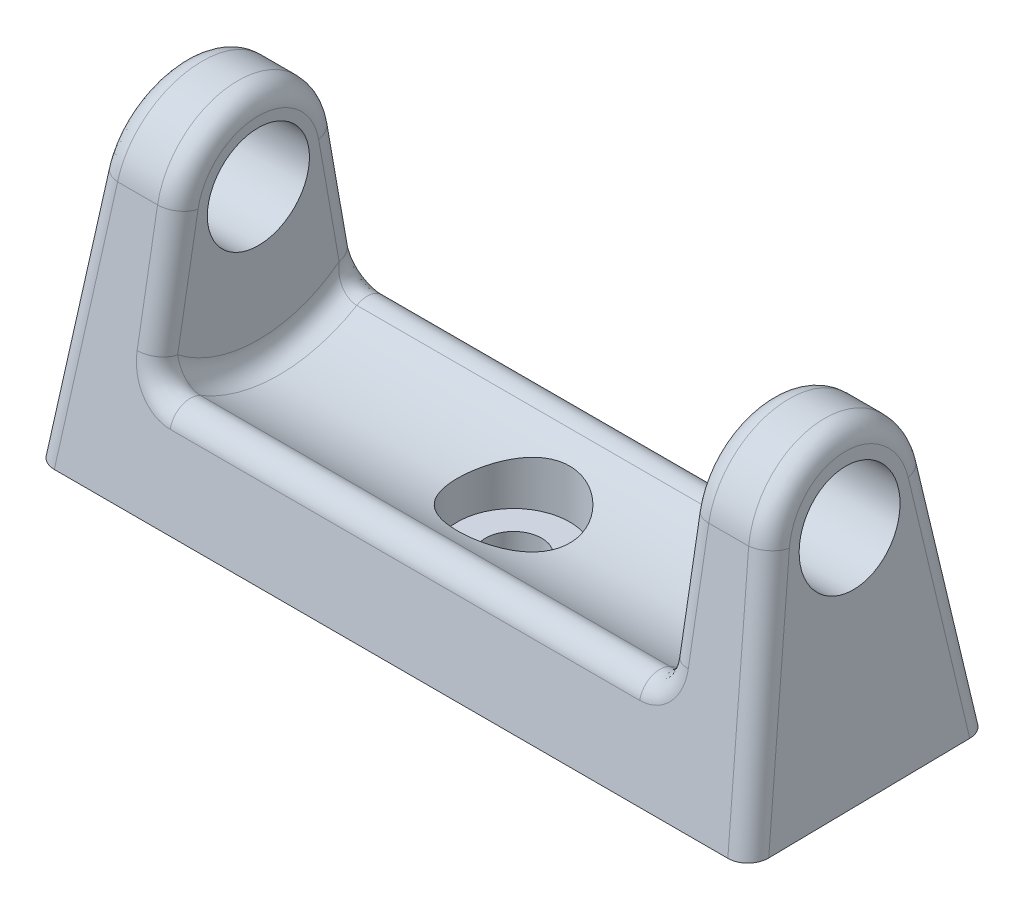
SolidWorks part; units mm, degrees
note: The reader was unsure of these and kept them because the rebuilt part matched: shared geometry of "Sketch3<6>".
ref_plane "Front Plane" through (0, 0, 0) normal (0, 0, 1) x (1, 0, 0)
ref_plane "Top Plane" through (0, 0, 0) normal (0, 1, 0) x (1, 0, 0)
ref_plane "Right Plane" through (0, 0, 0) normal (1, 0, 0) x (0, 0, -1)
sketch "Sketch2" plane through (0, 0, 0) normal (0, 1, 0) x (1, 0, 0)
  line L1 (-35, -12) -> (35, -12)
  line L2 (-35, -12) -> (-35, 12)
  line L3 (-35, 12) -> (35, 12)
  line L4 (35, -12) -> (35, 12)
  line L5 (-35, -12) -> (35, 12) construction
  line L6 (-35, 12) -> (35, -12) construction
  point P0 (0, 0)
  dimension "D1" = 70
  dimension "D2" = 24
extrude "Boss-Extrude1" add sketch "Sketch2" along normal blind 13
sketch "Sketch3" plane through (-35, 0, 0) normal (-1, 0, 0) x (0, 0, 1)
  line L0 (-7.8786, 23.3883) -> (-12, 0)
  line L1 (7.8786, 23.3883) -> (12, 0)
  line L2 (-12, 0) -> (12, 0)
  circle A0 centre (0, 22) radius 8
  circle A1 centre (0, 22) radius 5
  line M6 (-12, 0) -> (12, 0)
  line M7 (12, 0) -> (12, 13)
  line M8 (12, 13) -> (-12, 13)
  line M9 (-12, 13) -> (-12, 0)
  dimension "D1" = 16
  dimension "D3" = 22
  dimension "D5" = 10
  dimension "D2" = 22
  dimension "D4" = 24
extrude "Cut-Extrude2" cut sketch "Sketch3" against normal blind 70 contours L0 M8 M9 | L1 M8 M7
sketch "Sketch7" plane through (-35, 0, 0) normal (-1, 0, 0) x (0, 0, 1)
  line L0 (-12, 0) -> (12, 0) construction
  circle A0 centre (0, 22) radius 15
  dimension "D1" = 30
  dimension "D2" = 22
  dimension "D3" = 22
extrude "Cut-Extrude3" cut sketch "Sketch7" against normal blind 70
extrude "Boss-Extrude2" add sketch "Sketch3<6>" against normal blind 10 contours A0 A1 | L1 L0 M8 M6 | A0 L0 L1 M8
sketch "Sketch3<6>" plane through (-35, 0, 0) normal (-1, 0, 0) x (0, 0, 1) same geometry as "Sketch3"
sketch "Sketch9" plane through (0, 2.0509, 11.6386) normal (0, 0.1735, 0.9848) x (1, 0, 0)
  line L0 (-35, -2.0825) -> (-35, 41.5951)
  line L1 (-35, -2.0825) -> (-31.1735, 41.6551)
  line L2 (-35, 41.5951) -> (-31.1735, 41.6551)
  dimension "D1" = 5
  dimension "D2" = 43.6776
  dimension "D3" = 43.7376
extrude "Cut-Extrude7" cut sketch "Sketch9" against normal blind 26
mirror "Mirror1" about plane through (0, 0, 0) normal (1, 0, 0) of "Boss-Extrude2", "Cut-Extrude7"
fillet "Fillet1" radius 2 16 edges at (-33.6593, 11.6942, -9.9393) (25, 17.1403, -8.9796) (25, 17.1403, 8.9796) (-25, 17.1403, -8.9796) (25, 7, 0) (33.6593, 11.6942, -9.9393) (33.9611, 11.6942, 9.9393) (32.233, 30, 0) (25, 30, 0) (0, 10.8923, -10.0806) (-25, 7, 0) (0, 10.8923, 10.0806) (-33.9611, 11.6942, 9.9393) (-25, 17.1403, 8.9796) (-32.233, 30, 0) (-25, 30, 0)
hole_wizard "CBORE for M5 Pan Head Machine Screw1" positions "3DSketch2" profile "Sketch10" counterbore size "M5" standard "ANSI Metric" end condition up to next
sketch3d "3DSketch2"
  point P0 (0, 7, 0)
sketch "Sketch10" plane through (0, 7, 0) normal (1, 0, 0) x (0, 0, 1)
  line L0 (0, 0) -> (0, 7)
  line L1 (0, 7) -> (2.75, 7)
  line L3 (2.75, 7) -> (2.75, 3.7)
  line L4 (2.75, 3.7) -> (5.5, 3.7)
  line L5 (5.5, 3.7) -> (5.5, 0)
  line L7 (5.5, 0) -> (0, 0)
  line L11 (0, -6.35) -> (0, 107.95) construction
  dimension "Thru Hole Dia." = 5.5
  dimension "Thru Hole Depth" = 7
  dimension "C'Bore Dia." = 11
  dimension "C'Bore Depth" = 3.7
